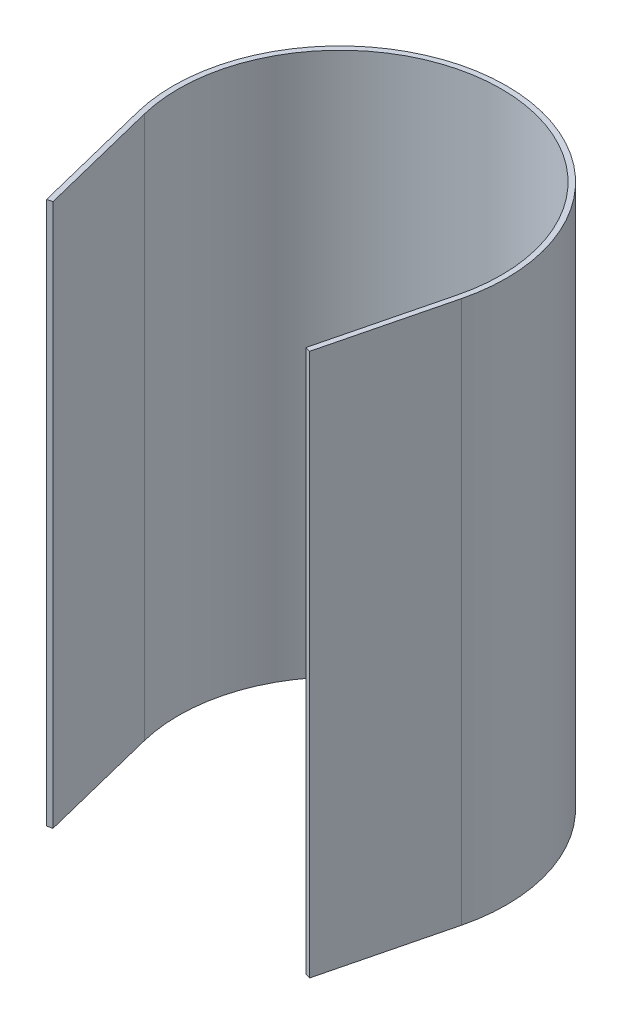
SolidWorks part; units mm, degrees
ref_plane "Front Plane" through (0, 0, 0) normal (0, 0, 1) x (1, 0, 0)
ref_plane "Top Plane" through (0, 0, 0) normal (0, 1, 0) x (1, 0, 0)
ref_plane "Right Plane" through (0, 0, 0) normal (1, 0, 0) x (0, 0, -1)
sketch "Electronics Glass Sketch" plane through (0, 0, 0) normal (0, 1, 0) x (1, 0, 0)
  line L0 (0, 0) -> (0, 609.6) construction
  line L1 (0, 0) -> (609.6, 0) construction
  line L2 (0, 0) -> (0, -1100) construction
  line L3 (0, -1100) -> (343.7362, -1100) construction
  line L4 (610.9566, -152.0795) -> (496.7542, -610.8707)
  line L5 (496.7542, -610.8707) -> (382.5517, -1069.662) construction
  line L6 (477.3464, -606.0397) -> (496.7542, -610.8707)
  line L7 (0, 0) -> (609.6, 0) construction
  line L8 (0, 0) -> (591.5488, -147.2485) construction
  line L9 (591.5488, -147.2485) -> (477.3464, -606.0397)
  line L10 (0, 609.6) -> (0, 629.6) construction
  line L11 (-477.3464, -606.0397) -> (-496.7542, -610.8707)
  line L12 (-591.5488, -147.2485) -> (-477.3464, -606.0397)
  line L13 (-610.9566, -152.0795) -> (-496.7542, -610.8707)
  arc A0 (610.9566, -152.0795) -> (-610.9566, -152.0795) centre (0, 0) ccw
  arc A1 (609.6, 0) -> (-609.6, 0) centre (0, 0) ccw
  arc A2 (591.5488, -147.2485) -> (609.6, 0) centre (0, 0) ccw
  arc A3 (-591.5488, -147.2485) -> (-609.6, 0) centre (0, 0) cw
  arc A4 (343.7362, -1100) -> (382.5517, -1069.662) centre (343.7362, -1060) ccw construction
  point P17 (375, -1100)
  dimension "D1" = 20
  dimension "D5" = 40
  dimension "D2" = 1100
  dimension "D3" = 375
  dimension "D4" = 20
  dimension "PressureHull_OuterRadius" = 609.6
extrude "Electronics Glass Extrude" add sketch "Electronics Glass Sketch" along normal blind 2050
equation "\"PressureHull_InnerRadius\"= 546.1mm"
equation "\"PressureHull_OuterRadius\"= 609.6mm"
equation "\"InnerShell_InnerRadius\"= 543mm"
